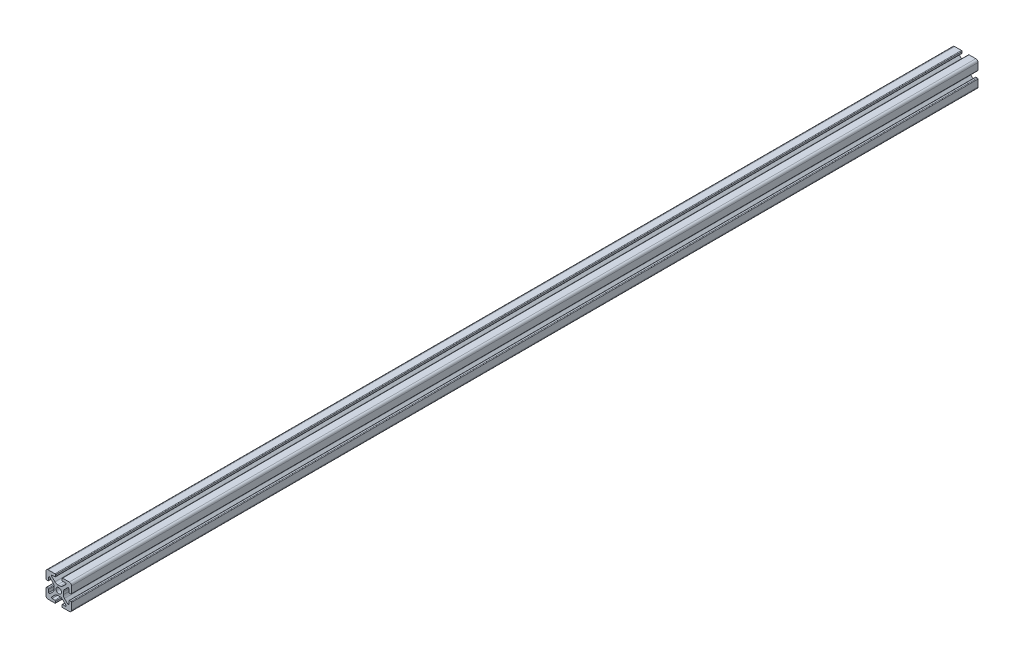
SolidWorks part; units mm, degrees
ref_plane "Front Plane" through (0, 0, 0) normal (0, 0, 1) x (1, 0, 0)
ref_plane "Top Plane" through (0, 0, 0) normal (0, 1, 0) x (1, 0, 0)
ref_plane "Right Plane" through (0, 0, 0) normal (1, 0, 0) x (0, 0, -1)
sketch "Sketch2" plane through (0, 0, 0) normal (0, 0, 1) x (1, 0, 0)
  line L0 (0, 10) -> (0, -10) construction
  line L1 (-10, 0) -> (10, 0) construction
  line L2 (2.5, -10) -> (10, -10)
  line L3 (10, -10) -> (10, -2.5)
  line L4 (2.5, -10) -> (2.5, -7.9246)
  line L5 (2.5, -7.9246) -> (6.4571, -7.9246)
  line L6 (6.4571, -7.9246) -> (2.1325, -3.6)
  line L7 (0, 0) -> (10, -10) construction
  line L8 (10, -2.5) -> (7.9246, -2.5)
  line L9 (7.9246, -2.5) -> (7.9246, -6.4571)
  line L10 (7.9246, -6.4571) -> (3.6, -2.1325)
  line L11 (5.7623, -4.2948) -> (4.2948, -5.7623) construction
  circle A0 centre (0, 0) radius 2.15
  arc A1 (5.25, -7.9246) -> (5.6036, -7.0711) centre (5.25, -7.4246) ccw construction
  point P8 (0, -3.6)
  point P16 (5.0286, -5.0286)
  dimension "Center Hole Diameter" = 4.3
  dimension "D3" = 0.5
  dimension "Rail Height" = 20
  dimension "Rail Width" = 20
  dimension "T-Slot Width" = 5
  dimension "Slot Depth" = 6.4
  dimension "Slot Inner Width" = 11.5
sketch "Sketch3" plane through (0, 0, 0) normal (1, 0, 0) x (0, 0, -1)
  line L0 (-355.36, -10) -> (355.36, -10) construction
  line L1 (-329.96, 0) -> (329.96, 0) construction
  line L2 (0, 10) -> (0, -10) construction
  line L3 (0, 10) -> (0, -10) construction
  point P6 (-329.96, 0)
  point P8 (329.96, 0)
  dimension "Length" = 710.72
  dimension "D1" = 25.4
sketch "Sketch4" plane through (0, 0, 0) normal (0, 0, 1) x (1, 0, 0)
  line L0 (3, -10) -> (8.25, -10)
  line L1 (2.5, -10) -> (10, -10) construction
  line L2 (2.5, -10) -> (2.5, -7.9246) construction
  line L3 (2.5, -7.9246) -> (6.4571, -7.9246) construction
  line L4 (2.5, -8.4246) -> (2.5, -9.5)
  line L5 (3, -7.9246) -> (5.25, -7.9246)
  line L6 (0, -3.6) -> (0.8898, -3.6)
  line L7 (6.4571, -7.9246) -> (2.1325, -3.6) construction
  line L8 (3.0112, -4.4787) -> (5.6036, -7.0711)
  line L9 (10, -10) -> (10, -2.5) construction
  line L10 (7.9246, -6.4571) -> (3.6, -2.1325) construction
  line L11 (7.9246, -2.5) -> (7.9246, -6.4571) construction
  line L12 (7.9246, -5.25) -> (7.9246, -3)
  line L13 (10, -2.5) -> (7.9246, -2.5) construction
  line L14 (8.4246, -2.5) -> (9.5, -2.5)
  line L15 (10, -3) -> (10, -8.25)
  line L16 (7.0711, -5.6036) -> (4.4787, -3.0112)
  line L17 (3.6, 0) -> (3.6, -0.8898)
  line L18 (-10, 0) -> (10, 0) construction
  line L19 (0, -3.6) -> (0, -2.15)
  line L20 (0, 10) -> (0, -10) construction
  line L21 (3.6, 0) -> (2.15, 0)
  arc A0 (2.5, -9.5) -> (3, -10) centre (3, -9.5) ccw
  arc A1 (5.25, -7.9246) -> (5.6036, -7.0711) centre (5.25, -7.4246) ccw construction
  arc A2 (2.5, -8.4246) -> (3, -7.9246) centre (3, -8.4246) cw
  arc A3 (5.25, -7.9246) -> (5.6036, -7.0711) centre (5.25, -7.4246) ccw
  arc A4 (0.8898, -3.6) -> (3.0112, -4.4787) centre (0.8898, -6.6) cw
  arc A5 (8.25, -10) -> (10, -8.25) centre (8.25, -8.25) ccw
  arc A6 (7.0711, -5.6036) -> (7.9246, -5.25) centre (7.4246, -5.25) ccw
  arc A7 (7.9246, -3) -> (8.4246, -2.5) centre (8.4246, -3) cw
  arc A8 (9.5, -2.5) -> (10, -3) centre (9.5, -3) cw
  arc A9 (4.4787, -3.0112) -> (3.6, -0.8898) centre (6.6, -0.8898) cw
  circle A10 centre (0, 0) radius 2.15 construction
  arc A11 (0, -2.15) -> (2.15, 0) centre (0, 0) ccw
  dimension "D1" = 1.75
  dimension "D2" = 3
extrude "Boss-Extrude1" add sketch "Sketch4" along normal mid plane 710.72
mirror "Mirror1" about plane through (0, 0, 0) normal (1, 0, 0) of bodies 134
mirror "Mirror2" about plane through (0, 0, 0) normal (0, 1, 0) of bodies 135
equation "\"D3@Sketch2\"=\"T-Slot Width@Sketch2\"*0.1"
equation "\"D1@Sketch4\"=\"D3@Sketch2\"*3.5"
equation "\"D2@Sketch4\"=\"D3@Sketch2\"*6"
equation "\"D1@Boss-Extrude1\"=\"Length@Sketch3\""
